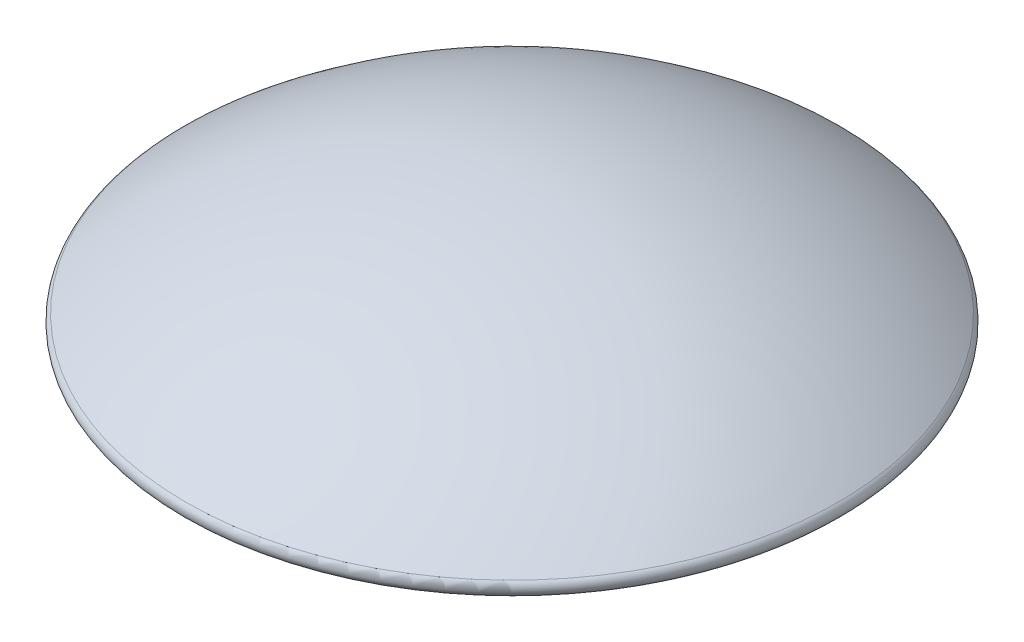
SolidWorks part; units mm, degrees
ref_plane "Ebene vorne" through (0, 0, 0) normal (0, 0, 1) x (1, 0, 0)
ref_plane "Ebene oben" through (0, 0, 0) normal (0, 1, 0) x (1, 0, 0)
ref_plane "Ebene rechts" through (0, 0, 0) normal (1, 0, 0) x (0, 0, -1)
sketch "Skizze1" plane through (0, 0, 0) normal (1, 0, 0) x (0, 0, -1)
  line L0 (0, 12.0655) -> (0, -10.1791) construction
  line L1 (-17.4926, 0) -> (19.3801, 0) construction
  line L2 (-8, 0) -> (-5, 0)
  line L3 (-5, 0) -> (-5, -1)
  line L4 (-5, -1) -> (-4, -1)
  line L5 (-4, -1) -> (-4, 0)
  line L6 (-4, 0) -> (0, 0)
  line L7 (0, 0) -> (0, 3)
  arc A0 (-8, 0) -> (0, 3) centre (0, -9.1667) cw
  dimension "D1" = 10
  dimension "D2" = 8
  dimension "D3" = 1
  dimension "D4" = 16
  dimension "D5" = 3
revolve "Rotation1" add sketch "Skizze1" angle 360 about L0
fillet "Verrundung1" radius 0.2 1 edges at (0, 0, 8)
chamfer "Fase1" distance 0.2 angle 45 4 edges at (0, 0, 5) (0, 0, 4) (0, -1, 5) (0, -1, 4)
ref_axis "Achse1" through (0, -1.2, 0) along (0, 1, 0)
